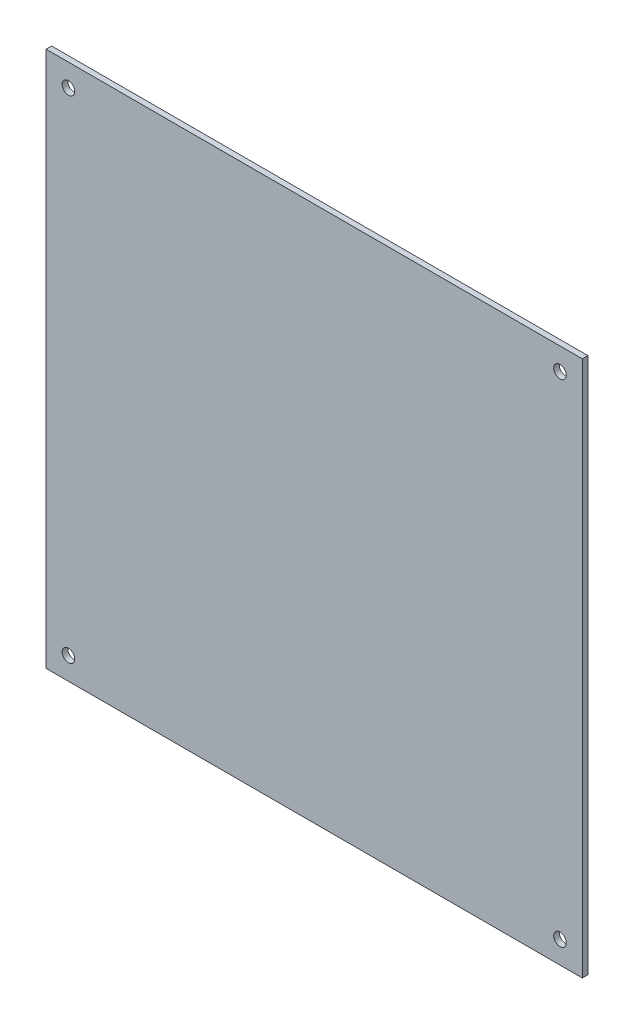
SolidWorks part; units mm, degrees
material "Acrylic (Medium-high impact)"
ref_plane "Front Plane" through (0, 0, 0) normal (0, 0, 1) x (1, 0, 0)
ref_plane "Top Plane" through (0, 0, 0) normal (0, 1, 0) x (1, 0, 0)
ref_plane "Right Plane" through (0, 0, 0) normal (1, 0, 0) x (0, 0, -1)
sketch "Sketch1" plane through (0, 0, 0) normal (0, 0, 1) x (1, 0, 0)
  line L1 (0, 0) -> (304.8, 0)
  line L2 (0, 0) -> (0, -304.8)
  line L3 (0, -304.8) -> (304.8, -304.8)
  line L4 (304.8, 0) -> (304.8, -304.8)
  dimension "D1" = 304.8
  dimension "D2" = 304.8
extrude "Boss-Extrude1" add sketch "Sketch1" along normal blind 3.175
sketch "Sketch2" plane through (0, 0, 3.175) normal (0, 0, 1) x (1, 0, 0)
  line L0 (152.4, 0) -> (152.4, -304.8) construction
  line L1 (304.8, 0) -> (0, 0) construction
  line L2 (0, -304.8) -> (304.8, -304.8) construction
  line L3 (0, -152.4) -> (304.8, -152.4) construction
  line L4 (0, 0) -> (0, -304.8) construction
  line L5 (304.8, -304.8) -> (304.8, 0) construction
  point P12 (12.7, -12.7)
  point P13 (0, 0)
  point P14 (292.1, -12.7)
  point P15 (0, 0)
  point P16 (0, 0)
  point P17 (12.7, -292.1)
  point P18 (292.1, -292.1)
  dimension "D1" = 12.7
  dimension "D2" = 12.7
hole_wizard "1/4 Clearance Hole1" positions "Sketch2" profile "Sketch3" hole size "1/4" standard "ANSI Inch" end condition up to next
sketch "Sketch3" plane through (292.1, -292.1, 3.175) normal (1, 0, 0) x (0, -1, 0)
  line L0 (0, 0) -> (0, 3.175)
  line L1 (0, 3.175) -> (3.5712, 3.175)
  line L2 (3.5712, 3.175) -> (3.5712, 0)
  line L5 (3.5712, 0) -> (0, 0)
  line L11 (0, -6.35) -> (0, 107.95) construction
  dimension "Thru Hole Dia." = 7.1425
  dimension "Thru Hole Depth" = 3.175
